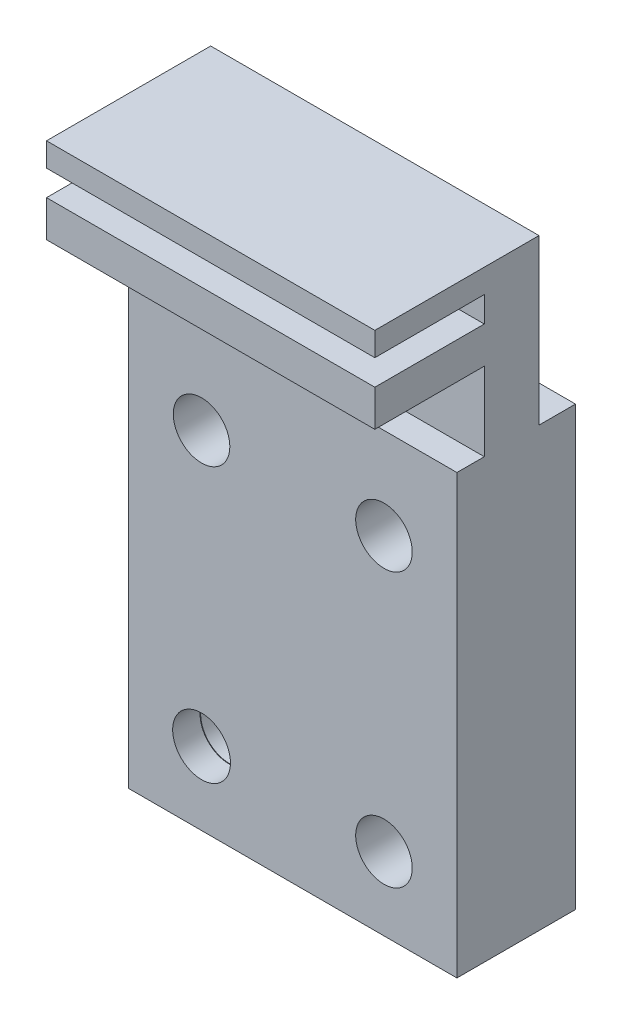
SolidWorks part; units mm, degrees
ref_plane "Ebene vorne" through (0, 0, 0) normal (0, 0, 1) x (1, 0, 0)
ref_plane "Ebene oben" through (0, 0, 0) normal (0, 1, 0) x (1, 0, 0)
ref_plane "Ebene rechts" through (0, 0, 0) normal (1, 0, 0) x (0, 0, -1)
sketch "Skizze1" plane through (0, 0, 0) normal (0, 0, 1) x (1, 0, 0)
  line L0 (10.3603, 19.5) -> (-9.5856, 19.5) construction
  line L1 (-5, 7.5) -> (5, 7.5) construction
  line L2 (-5, 7.5) -> (-5, -7.5) construction
  line L3 (-5, -7.5) -> (5, -7.5) construction
  line L4 (5, 7.5) -> (5, -7.5) construction
  line L5 (-9, 18.8) -> (9, 18.8)
  line L6 (-9, -11.5) -> (9, -11.5)
  line L7 (-9, -11.5) -> (-9, 21.5)
  line L8 (-9, 21.5) -> (9, 21.5)
  line L9 (9, -11.5) -> (9, 21.5)
  line L10 (-9, 20.2) -> (9, 20.2)
  line L11 (-9, 16.8) -> (9, 16.8)
  circle A0 centre (-5, 7.5) radius 1.55
  circle A1 centre (5, 7.5) radius 1.55
  circle A2 centre (5, -7.5) radius 1.55
  circle A3 centre (-5, -7.5) radius 1.55
  point P4 (0, 7.5)
  point P6 (5, 0)
  point P17 (0, -11.5)
  dimension "D3" = 3.1
  dimension "D1" = 10
  dimension "D2" = 15
  dimension "D4" = 12
  dimension "D5" = 4
  dimension "D6" = 4
  dimension "D7" = 2
  dimension "D8" = 0.7
  dimension "D9" = 0.7
  dimension "D10" = 2
extrude "Aufsatz-Linear austragen3" add sketch "Skizze1" against normal blind 5 contours L7 L10 L9 L8 | L10 L7 L5 L9 | L7 L11 L9 L5 | L11 L7 L6 L9 A3 A2 A1 A0 region at (0, 19.5, 0) region at (0, 17.8, 0) region at (0, 2.817, 0) region at (0, 20.85, 0)
extrude "Aufsatz-Linear austragen4" add sketch "Skizze1<4>" along normal blind 6 contours L7 L10 L9 L8 | L7 L11 L9 L5 region at (0, 17.8, 0) region at (0, 20.85, 0)
sketch "Skizze1<4>" plane through (0, 0, 0) normal (0, 0, 1) x (1, 0, 0) same geometry as "Skizze1"
sketch "Skizze2" plane through (9, 0, 0) normal (1, 0, 0) x (0, 0, -1)
  line L6 (5, 21.5) -> (3, 21.5)
  line L7 (5, 21.5) -> (5, 12.5)
  line L8 (5, 12.5) -> (3, 12.5)
  line L9 (3, 21.5) -> (3, 12.5)
  dimension "D1" = 2
  dimension "D2" = 9
extrude "Schnitt-Linear austragen1" cut sketch "Skizze2" against normal through all
sketch "Skizze3" plane through (0, 0, 0) normal (0, 0, 1) x (1, 0, 0)
  line L0 (-9, -11.5) -> (-9, 16.8) construction
  line L1 (9, -11.5) -> (-9, -11.5)
  line L2 (9, -11.5) -> (9, 12.5)
  line L3 (9, 12.5) -> (-9, 12.5)
  line L4 (-9, -11.5) -> (-9, 12.5)
  circle A0 centre (-5, 7.5) radius 1.55
  circle A1 centre (5, 7.5) radius 1.55
  circle A2 centre (-5, -7.5) radius 1.5837
  circle A3 centre (5, -7.5) radius 1.55
  dimension "D1" = 0
extrude "Aufsatz-Linear austragen5" add sketch "Skizze3" along normal blind 1.5
